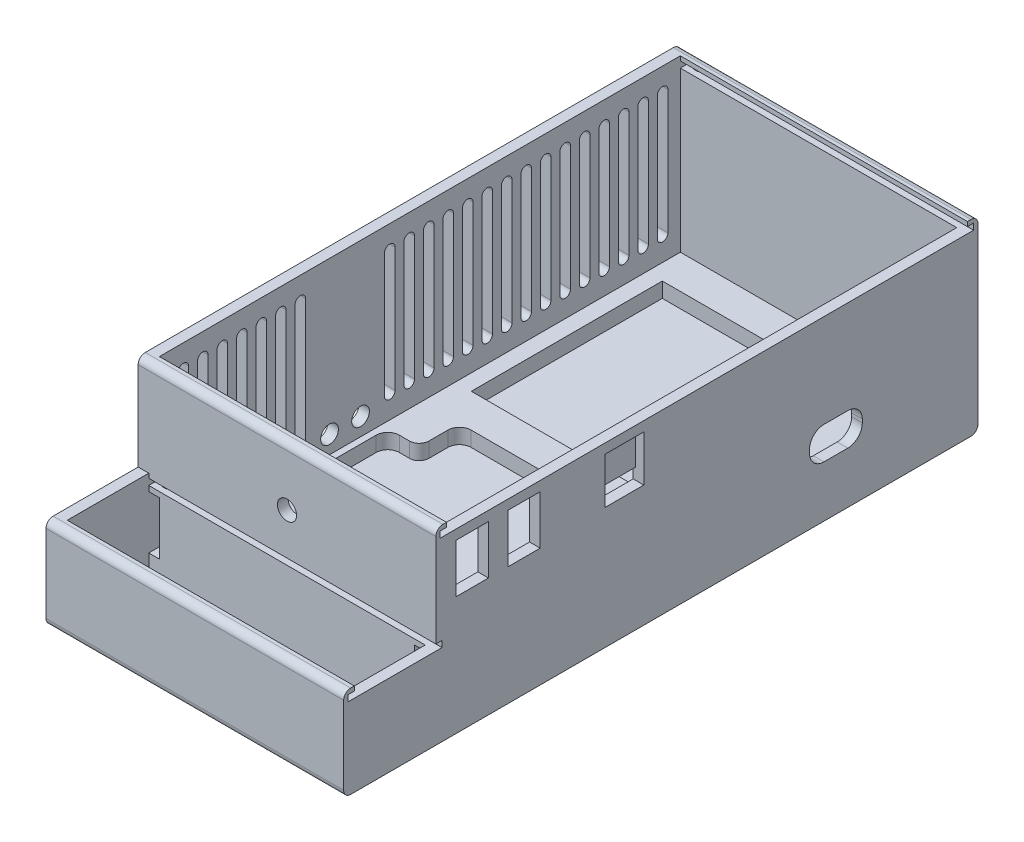
SolidWorks part; units mm, degrees
ref_plane "Front Plane" through (0, 0, 0) normal (0, 0, 1) x (1, 0, 0)
ref_plane "Top Plane" through (0, 0, 0) normal (0, 1, 0) x (1, 0, 0)
ref_plane "Right Plane" through (0, 0, 0) normal (1, 0, 0) x (0, 0, -1)
sketch "Sketch1" plane through (0, 0, 0) normal (0, 1, 0) x (1, 0, 0)
  line L5 (0, 0) -> (100, 0)
  line L6 (0, 0) -> (0, 187)
  line L7 (0, 187) -> (100, 187)
  line L8 (100, 0) -> (100, 187)
  dimension "D1" = 100
  dimension "D2" = 187
extrude "Boss-Extrude1" add sketch "Sketch1" against normal blind 5
sketch "Sketch2" plane through (0, 0, 0) normal (0, 1, 0) x (1, 0, 0)
  line L0 (0, 187) -> (0, 0) construction
  line L1 (11, 11) -> (89, 11)
  line L2 (11, 11) -> (11, 34)
  line L3 (11, 34) -> (89, 34)
  line L4 (89, 11) -> (89, 34)
  line L5 (0, 0) -> (100, 0) construction
  dimension "D1" = 78
  dimension "D2" = 23
  dimension "D3" = 11
  dimension "D4" = 11
extrude "Cut-Extrude1" cut sketch "Sketch2" against normal blind 2.5
sketch "Sketch3" plane through (0, 0, 0) normal (0, 1, 0) x (1, 0, 0)
  line L0 (11, 34) -> (89, 34)
  line L1 (89, 34) -> (89, 11)
  line L2 (89, 11) -> (11, 11)
  line L3 (11, 11) -> (11, 34)
  line L4 (8, 8) -> (8, 37)
  line L5 (8, 37) -> (92, 37)
  line L6 (92, 37) -> (92, 8)
  line L7 (92, 8) -> (8, 8)
  dimension "D1" = 3
extrude "Boss-Extrude2" add sketch "Sketch3" along normal blind 18
sketch "Sketch4" plane through (0, 0, 0) normal (0, 1, 0) x (1, 0, 0)
  line L1 (21.915, 57) -> (31.915, 57) construction
  line L2 (31.915, 47) -> (76.965, 47)
  line L3 (21.915, 107.77) -> (21.915, 102.4)
  line L4 (92, 37) -> (8, 37) construction
  line L5 (24.915, 110.77) -> (76.965, 110.77)
  line L7 (18.915, 99.4) -> (16.035, 99.4)
  line L8 (13.035, 96.4) -> (13.035, 82.01)
  line L9 (86.965, 100.77) -> (86.965, 57)
  line L10 (16.035, 79.01) -> (18.915, 79.01)
  line L11 (13.035, 89.205) -> (0, 89.205) construction
  line L12 (21.915, 76.01) -> (21.915, 57)
  line L14 (86.965, 78.885) -> (100, 78.885) construction
  line L15 (100, 0) -> (100, 187) construction
  line L16 (0, 187) -> (0, 0) construction
  arc A0 (21.915, 57) -> (31.915, 47) centre (31.915, 57) ccw
  arc A6 (24.915, 110.77) -> (21.915, 107.77) centre (24.915, 107.77) ccw
  arc A7 (21.915, 102.4) -> (18.915, 99.4) centre (18.915, 102.4) cw
  arc A8 (16.035, 99.4) -> (13.035, 96.4) centre (16.035, 96.4) ccw
  arc A9 (13.035, 82.01) -> (16.035, 79.01) centre (16.035, 82.01) ccw
  arc A10 (18.915, 79.01) -> (21.915, 76.01) centre (18.915, 76.01) cw
  arc A11 (86.965, 100.77) -> (76.965, 110.77) centre (76.965, 100.77) ccw
  arc A12 (76.965, 47) -> (86.965, 57) centre (76.965, 57) ccw
  point P27 (86.965, 110.77)
  point P29 (86.965, 47)
  dimension "D6" = 62.05
  dimension "D10" = 14.39
  dimension "D1" = 3
  dimension "D2" = 3
  dimension "D8" = 3
  dimension "D9" = 2.88
  dimension "D4" = 10
  dimension "D5" = 10
  dimension "D3" = 10
  dimension "D7" = 10
  dimension "D11" = 5.37
  dimension "D12" = 19.01
  dimension "D13" = 45.05
extrude "Cut-Extrude2" cut sketch "Sketch4" against normal blind 4.25 contours A0 L2 A12 L9 A11 L5 A6 L3 A7 L7 A8 L8 A9 L10 A10 L12
sketch "Sketch7" plane through (0, -2.5, 0) normal (0, 1, 0) x (1, 0, 0)
  line L0 (11, 34) -> (34, 11)
  line L1 (11, 11) -> (89, 11) construction
  line L2 (12, 34) -> (35, 11)
  line L3 (12, 34) -> (13, 34)
  line L5 (11, 11) -> (11.5217, 11)
  line L6 (89, 34) -> (89, 33)
  line L7 (13, 34) -> (36, 11)
  line L8 (14, 34) -> (37, 11)
  line L9 (15, 34) -> (38, 11)
  line L10 (16, 34) -> (39, 11)
  line L11 (17, 34) -> (40, 11)
  line L12 (18, 34) -> (41, 11)
  line L13 (19, 34) -> (42, 11)
  line L14 (20, 34) -> (43, 11)
  line L15 (21, 34) -> (44, 11)
  line L16 (22, 34) -> (45, 11)
  line L17 (23, 34) -> (46, 11)
  line L18 (24, 34) -> (47, 11)
  line L19 (25, 34) -> (48, 11)
  line L20 (26, 34) -> (49, 11)
  line L21 (27, 34) -> (50, 11)
  line L22 (28, 34) -> (51, 11)
  line L23 (29, 34) -> (52, 11)
  line L24 (30, 34) -> (53, 11)
  line L25 (31, 34) -> (54, 11)
  line L26 (32, 34) -> (55, 11)
  line L27 (33, 34) -> (56, 11)
  line L28 (34, 34) -> (57, 11)
  line L29 (35, 34) -> (58, 11)
  line L30 (36, 34) -> (59, 11)
  line L31 (37, 34) -> (60, 11)
  line L32 (38, 34) -> (61, 11)
  line L33 (39, 34) -> (62, 11)
  line L34 (40, 34) -> (63, 11)
  line L35 (41, 34) -> (64, 11)
  line L36 (42, 34) -> (65, 11)
  line L37 (43, 34) -> (66, 11)
  line L38 (44, 34) -> (67, 11)
  line L39 (45, 34) -> (68, 11)
  line L40 (46, 34) -> (69, 11)
  line L41 (47, 34) -> (70, 11)
  line L42 (48, 34) -> (71, 11)
  line L43 (49, 34) -> (72, 11)
  line L44 (50, 34) -> (73, 11)
  line L45 (51, 34) -> (74, 11)
  line L46 (52, 34) -> (75, 11)
  line L47 (53, 34) -> (76, 11)
  line L48 (54, 34) -> (77, 11)
  line L49 (55, 34) -> (78, 11)
  line L50 (56, 34) -> (79, 11)
  line L51 (57, 34) -> (80, 11)
  line L52 (58, 34) -> (81, 11)
  line L53 (59, 34) -> (82, 11)
  line L54 (60, 34) -> (83, 11)
  line L55 (61, 34) -> (84, 11)
  line L56 (62, 34) -> (85, 11)
  line L57 (63, 34) -> (86, 11)
  line L58 (64, 34) -> (87, 11)
  line L59 (65, 34) -> (88, 11)
  line L60 (66, 34) -> (89, 11)
  line L61 (67, 34) -> (89, 12)
  line L62 (68, 34) -> (89, 13)
  line L63 (69, 34) -> (89, 14)
  line L64 (70, 34) -> (89, 15)
  line L65 (71, 34) -> (89, 16)
  line L66 (72, 34) -> (89, 17)
  line L67 (73, 34) -> (89, 18)
  line L68 (74, 34) -> (89, 19)
  line L69 (75, 34) -> (89, 20)
  line L70 (76, 34) -> (89, 21)
  line L71 (77, 34) -> (89, 22)
  line L72 (78, 34) -> (89, 23)
  line L73 (79, 34) -> (89, 24)
  line L74 (80, 34) -> (89, 25)
  line L75 (81, 34) -> (89, 26)
  line L76 (82, 34) -> (89, 27)
  line L77 (83, 34) -> (89, 28)
  line L78 (84, 34) -> (89, 29)
  line L79 (85, 34) -> (89, 30)
  line L80 (86, 34) -> (89, 31)
  line L81 (87, 34) -> (89, 32)
  line L82 (88, 34) -> (89, 33)
  line L83 (11, 32.9783) -> (32.9783, 11)
  line L84 (11, 31.9565) -> (31.9565, 11)
  line L85 (11, 30.9348) -> (30.9348, 11)
  line L86 (11, 29.913) -> (29.913, 11)
  line L87 (11, 28.8913) -> (28.8913, 11)
  line L88 (11, 27.8696) -> (27.8696, 11)
  line L89 (11, 26.8478) -> (26.8478, 11)
  line L90 (11, 25.8261) -> (25.8261, 11)
  line L91 (11, 24.8043) -> (24.8043, 11)
  line L92 (11, 23.7826) -> (23.7826, 11)
  line L93 (11, 22.7609) -> (22.7609, 11)
  line L94 (11, 21.7391) -> (21.7391, 11)
  line L95 (11, 20.7174) -> (20.7174, 11)
  line L96 (11, 19.6956) -> (19.6956, 11)
  line L97 (11, 18.6739) -> (18.6739, 11)
  line L98 (11, 17.6522) -> (17.6522, 11)
  line L99 (11, 16.6304) -> (16.6304, 11)
  line L100 (11, 15.6087) -> (15.6087, 11)
  line L101 (11, 14.5869) -> (14.5869, 11)
  line L102 (11, 13.5652) -> (13.5652, 11)
  line L103 (11, 12.5435) -> (12.5435, 11)
  line L104 (11, 11.5217) -> (11.5217, 11)
  line L105 (12.5435, 11) -> (13.5652, 11)
  line L106 (11, 11.5217) -> (11, 11)
  line L107 (14.5869, 11) -> (15.6087, 11)
  line L108 (11, 13.5652) -> (11, 12.5435)
  line L110 (16.6304, 11) -> (17.6522, 11)
  line L111 (11, 16.6304) -> (11, 17.6522)
  line L112 (11, 18.6739) -> (11, 19.6956)
  line L113 (18.6739, 11) -> (19.6956, 11)
  line L114 (20.7174, 11) -> (21.7391, 11)
  line L115 (11, 20.7174) -> (11, 21.7391)
  line L116 (22.7609, 11) -> (23.7826, 11)
  line L117 (11, 22.7609) -> (11, 23.7826)
  line L118 (11, 24.8043) -> (11, 25.8261)
  line L119 (24.8043, 11) -> (25.8261, 11)
  line L120 (26.8478, 11) -> (27.8696, 11)
  line L121 (11, 26.8478) -> (11, 27.8696)
  line L122 (11, 28.8913) -> (11, 29.913)
  line L123 (11, 30.9348) -> (11, 31.9565)
  line L124 (28.8913, 11) -> (29.913, 11)
  line L125 (30.9348, 11) -> (31.9565, 11)
  line L126 (32.9783, 11) -> (34, 11)
  line L127 (35, 11) -> (36, 11)
  line L128 (11, 32.9783) -> (11, 34)
  line L129 (14, 34) -> (15, 34)
  line L130 (16, 34) -> (17, 34)
  line L131 (37, 11) -> (38, 11)
  line L132 (39, 11) -> (40, 11)
  line L133 (41, 11) -> (42, 11)
  line L134 (43, 11) -> (44, 11)
  line L135 (45, 11) -> (46, 11)
  line L136 (47, 11) -> (48, 11)
  line L137 (49, 11) -> (50, 11)
  line L138 (51, 11) -> (52, 11)
  line L139 (53, 11) -> (54, 11)
  line L140 (55, 11) -> (56, 11)
  line L141 (57, 11) -> (58, 11)
  line L142 (59, 11) -> (60, 11)
  line L143 (61, 11) -> (62, 11)
  line L144 (63, 11) -> (64, 11)
  line L145 (65, 11) -> (66, 11)
  line L146 (18, 34) -> (19, 34)
  line L147 (20, 34) -> (21, 34)
  line L148 (22, 34) -> (23, 34)
  line L149 (24, 34) -> (25, 34)
  line L150 (26, 34) -> (27, 34)
  line L151 (28, 34) -> (29, 34)
  line L152 (30, 34) -> (31, 34)
  line L153 (32, 34) -> (33, 34)
  line L154 (34, 34) -> (35, 34)
  line L155 (36, 34) -> (37, 34)
  line L156 (38, 34) -> (39, 34)
  line L157 (40, 34) -> (41, 34)
  line L158 (42, 34) -> (43, 34)
  line L159 (44, 34) -> (45, 34)
  line L160 (46, 34) -> (47, 34)
  line L161 (67, 11) -> (68, 11)
  line L162 (69, 11) -> (70, 11)
  line L163 (71, 11) -> (72, 11)
  line L164 (73, 11) -> (74, 11)
  line L165 (75, 11) -> (76, 11)
  line L166 (77, 11) -> (78, 11)
  line L167 (79, 11) -> (80, 11)
  line L168 (81, 11) -> (82, 11)
  line L169 (83, 11) -> (84, 11)
  line L170 (85, 11) -> (86, 11)
  line L171 (87, 11) -> (88, 11)
  line L172 (48, 34) -> (49, 34)
  line L173 (50, 34) -> (51, 34)
  line L174 (52, 34) -> (53, 34)
  line L175 (54, 34) -> (55, 34)
  line L176 (56, 34) -> (57, 34)
  line L177 (58, 34) -> (59, 34)
  line L178 (60, 34) -> (61, 34)
  line L179 (62, 34) -> (63, 34)
  line L180 (64, 34) -> (65, 34)
  line L181 (66, 34) -> (67, 34)
  line L182 (68, 34) -> (69, 34)
  line L183 (70, 34) -> (71, 34)
  line L184 (72, 34) -> (73, 34)
  line L185 (74, 34) -> (75, 34)
  line L186 (76, 34) -> (77, 34)
  line L187 (78, 34) -> (79, 34)
  line L188 (80, 34) -> (81, 34)
  line L189 (82, 34) -> (83, 34)
  line L190 (84, 34) -> (85, 34)
  line L191 (86, 34) -> (87, 34)
  line L192 (88, 34) -> (89, 34)
  line L193 (89, 12) -> (89, 11)
  line L194 (89, 14) -> (89, 13)
  line L195 (89, 16) -> (89, 15)
  line L196 (89, 18) -> (89, 17)
  line L197 (89, 20) -> (89, 19)
  line L198 (89, 22) -> (89, 21)
  line L199 (89, 24) -> (89, 23)
  line L200 (89, 26) -> (89, 25)
  line L201 (89, 28) -> (89, 27)
  line L202 (89, 30) -> (89, 29)
  line L203 (89, 32) -> (89, 31)
  line L204 (11, 15.6087) -> (11, 14.5869)
  dimension "D1" = 78
  dimension "D2" = 23
extrude "Cut-Extrude3" cut sketch "Sketch7" against normal blind 0.5
sketch "Sketch8" plane through (0, 0, -37) normal (0, 0, -1) x (-1, 0, 0)
  line L0 (-92, 18) -> (-92, 0) construction
  line L1 (-89, 1.5) -> (-86, 1.5)
  line L2 (-89, 1.5) -> (-89, 16.5)
  line L3 (-89, 16.5) -> (-86, 16.5)
  line L4 (-86, 1.5) -> (-86, 16.5)
  line L5 (-92, 18) -> (-8, 18) construction
  line L6 (-92, 0) -> (-8, 0) construction
  line L7 (-92, 18) -> (-8, 18) construction
  line L8 (-50, 18) -> (-50, 0) construction
  line L9 (-11, 16.5) -> (-14, 16.5)
  line L10 (-14, 1.5) -> (-14, 16.5)
  line L11 (-11, 1.5) -> (-14, 1.5)
  line L12 (-11, 1.5) -> (-11, 16.5)
  dimension "D1" = 3
  dimension "D2" = 1.5
  dimension "D3" = 1.5
  dimension "D4" = 3
extrude "Cut-Extrude4" cut sketch "Sketch8" against normal blind 3
sketch "Sketch9" plane through (8, 0, 0) normal (-1, 0, 0) x (0, 0, 1)
  line L0 (-37, 18) -> (-8, 18)
  line L1 (-8, 18) -> (-8, 21)
  line L2 (-8, 21) -> (-37, 21)
  line L3 (-37, 21) -> (-37, 18)
  dimension "D1" = 3
extrude "Boss-Extrude4" add sketch "Sketch9" against normal blind 3
sketch "Sketch10" plane through (11, 0, 0) normal (1, 0, 0) x (0, 0, -1)
  line L0 (9.25, 18) -> (8, 18)
  line L1 (8, 18) -> (8, 21)
  line L2 (8, 21) -> (11, 21)
  line L3 (8, 21) -> (37, 21) construction
  line L8 (11, 19.75) -> (11, 21)
  line L9 (11, 19.75) -> (9.25, 19.75)
  line L10 (9.25, 19.75) -> (9.25, 18)
  line L12 (8, 18) -> (37, 18) construction
  line L13 (22.5, 21) -> (22.5, 12.8527) construction
  line L22 (35.75, 19.75) -> (35.75, 18)
  line L23 (11, -3) -> (11, 18) construction
  line L24 (34, 19.75) -> (35.75, 19.75)
  line L25 (34, 19.75) -> (34, 21)
  line L26 (37, 21) -> (34, 21)
  line L27 (37, 18) -> (37, 21)
  line L28 (35.75, 18) -> (37, 18)
  dimension "D1" = 1.25
  dimension "D2" = 1.25
extrude "Boss-Extrude5" add sketch "Sketch10" along normal up to surface (81 mm away) up to face at (92, 9, -22.5)
sketch "Sketch12" plane through (0, 0, 0) normal (0, 1, 0) x (1, 0, 0)
  line L0 (0, 0) -> (100, 0)
  line L1 (100, 0) -> (100, 187)
  line L2 (100, 0) -> (100, 187) construction
  line L3 (92, 37) -> (92, 187) construction
  line L4 (100, 187) -> (0, 187) construction
  line L5 (8, 37) -> (8, 187) construction
  line L6 (100, 187) -> (92, 187)
  line L7 (92, 187) -> (92, 8)
  line L8 (92, 8) -> (8, 8)
  line L9 (8, 8) -> (8, 187)
  line L10 (8, 187) -> (0, 187)
  line L11 (0, 187) -> (0, 0)
extrude "Cut-Extrude5" cut sketch "Sketch12" against normal up to surface (5 mm away) up to face at (50, -5, -93.5)
sketch "Sketch13" plane through (0, 0, 0) normal (0, 1, 0) x (1, 0, 0)
  line L0 (8, 37) -> (8, 187)
  line L1 (8, 187) -> (92, 187)
  line L2 (92, 187) -> (92, 37)
  line L5 (11, 40) -> (11, 184)
  line L6 (11, 184) -> (89, 184)
  line L7 (89, 184) -> (89, 40)
  line L8 (11, 40) -> (11, 37)
  line L9 (89, 40) -> (89, 37)
  line L10 (11, 37) -> (8, 37)
  line L11 (89, 40) -> (11, 40) construction
  line L12 (92, 37) -> (8, 37) construction
  line L13 (89, 37) -> (92, 37)
  dimension "D1" = 3
extrude "Boss-Extrude6" add sketch "Sketch13" along normal blind 45
sketch "Sketch14" plane through (0, 0, 0) normal (0, 1, 0) x (1, 0, 0)
  line L11 (84.25, 174.17) -> (15.75, 174.17)
  line L16 (15.75, 120.77) -> (84.25, 120.77)
  line L17 (84.25, 120.77) -> (84.25, 174.17)
  line L20 (24.915, 110.77) -> (76.965, 110.77) construction
  line L22 (15.75, 147.47) -> (11, 147.47) construction
  line L24 (11, 37) -> (11, 184) construction
  line L27 (15.75, 120.77) -> (15.75, 174.17)
  line L28 (84.25, 147.47) -> (89, 147.47) construction
  line L29 (89, 184) -> (89, 37) construction
  dimension "D1" = 68.5
  dimension "D2" = 10
  dimension "D7" = 53.4
extrude "Cut-Extrude6" cut sketch "Sketch14" against normal blind 4.25
sketch "Sketch15" plane through (0, 21, 0) normal (0, 1, 0) x (1, 0, 0)
  line L6 (8, 37) -> (92, 37)
  line L7 (8, 37) -> (8, 34)
  line L8 (8, 34) -> (92, 34)
  line L9 (92, 37) -> (92, 34)
extrude "Boss-Extrude7" add sketch "Sketch15" along normal up to surface (24 mm away) up to face at (50, 45, -111.25)
sketch "Sketch16" plane through (0, 45, 0) normal (0, 1, 0) x (1, 0, 0)
  line L16 (92, 34) -> (8, 34)
  line L17 (8, 34) -> (8, 187)
  line L18 (8, 187) -> (92, 187)
  line L19 (11, 37) -> (92, 37)
  line L20 (92, 34) -> (92, 187) construction
  line L21 (92, 34) -> (92, 37)
  line L22 (11, 37) -> (11, 184)
  line L23 (11, 184) -> (92, 184)
  line L24 (92, 184) -> (92, 187)
extrude "Boss-Extrude8" add sketch "Sketch16" along normal blind 3
sketch "Sketch19" plane through (92, 0, 0) normal (1, 0, 0) x (0, 0, -1)
  line L0 (37, 46.75) -> (35.25, 46.75)
  line L1 (37, 48) -> (37, 45) construction
  line L2 (35.25, 46.75) -> (35.25, 45)
  line L3 (35.25, 45) -> (37, 45)
  line L4 (37, 45) -> (37, 46.75)
  line L5 (110.5, 45) -> (110.5, 48) construction
  line L6 (37, 45) -> (184, 45) construction
  line L7 (184, 45) -> (184, 46.75)
  line L8 (185.75, 45) -> (184, 45)
  line L9 (185.75, 46.75) -> (185.75, 45)
  line L10 (184, 46.75) -> (185.75, 46.75)
  line L11 (34, 48) -> (37, 48) construction
  line L12 (34, 19.75) -> (34, 48) construction
  dimension "D1" = 1.25
  dimension "D2" = 1.25
  dimension "D4" = 3
extrude "Cut-Extrude8" cut sketch "Sketch19" against normal up to surface (81 mm away) up to face at (11, 3.0077, -28.7231)
sketch "Sketch23" plane through (0, 0, -9.25) normal (0, 0, -1) x (-1, 0, 0)
  line L0 (-11, 18.875) -> (-14, 18.875) construction
  line L1 (-11, 18) -> (-11, 19.75) construction
  line L3 (-14.875, 19.5) -> (-13.125, 19.5)
  line L4 (-14.875, 19.5) -> (-14.875, 18.25)
  line L5 (-14.875, 18.25) -> (-13.125, 18.25)
  line L6 (-13.125, 19.5) -> (-13.125, 18.25)
  line L7 (-14.875, 19.5) -> (-13.125, 18.25) construction
  line L8 (-14.875, 18.25) -> (-13.125, 19.5) construction
  dimension "D1" = 3
  dimension "D2" = 1.75
  dimension "D3" = 1.25
extrude "Boss-Extrude9" add sketch "Sketch23" along normal blind 0.4
fillet "Fillet2" radius 0.4 2 edges at (13.125, 18.875, -9.65) (14.875, 18.875, -9.65)
sketch "Sketch40" plane through (0, 0, -35.75) normal (0, 0, 1) x (1, 0, 0)
  line L0 (11, 18.875) -> (14, 18.875) construction
  line L1 (11, 19.75) -> (11, 18) construction
  line L3 (13.125, 19.5) -> (14.875, 19.5)
  line L4 (13.125, 19.5) -> (13.125, 18.25)
  line L5 (13.125, 18.25) -> (14.875, 18.25)
  line L6 (14.875, 19.5) -> (14.875, 18.25)
  line L7 (13.125, 19.5) -> (14.875, 18.25) construction
  line L8 (13.125, 18.25) -> (14.875, 19.5) construction
  dimension "D1" = 3
  dimension "D2" = 1.25
  dimension "D3" = 1.75
extrude "Boss-Extrude14" add sketch "Sketch40" along normal blind 0.4
fillet "Fillet6" radius 0.4 2 edges at (14.875, 18.875, -35.35) (13.125, 18.875, -35.35)
sketch "Sketch25" plane through (0, 0, -35.25) normal (0, 0, -1) x (-1, 0, 0)
  line L0 (-11, 45.875) -> (-14, 45.875) construction
  line L1 (-11, 46.75) -> (-11, 45) construction
  line L3 (-13.125, 46.5) -> (-14.875, 46.5)
  line L4 (-13.125, 46.5) -> (-13.125, 45.25)
  line L5 (-13.125, 45.25) -> (-14.875, 45.25)
  line L6 (-14.875, 46.5) -> (-14.875, 45.25)
  line L7 (-13.125, 46.5) -> (-14.875, 45.25) construction
  line L8 (-13.125, 45.25) -> (-14.875, 46.5) construction
  dimension "D1" = 3
  dimension "D2" = 1.75
  dimension "D3" = 1.25
extrude "Boss-Extrude11" add sketch "Sketch25" along normal blind 0.4
fillet "Fillet4" radius 0.4 2 edges at (13.125, 45.875, -35.65) (14.875, 45.875, -35.65)
sketch "Sketch26" plane through (0, 0, -185.75) normal (0, 0, 1) x (1, 0, 0)
  line L0 (11, 45.875) -> (14, 45.875) construction
  line L1 (11, 45) -> (11, 46.75) construction
  line L3 (13.125, 46.5) -> (14.875, 46.5)
  line L4 (13.125, 46.5) -> (13.125, 45.25)
  line L5 (13.125, 45.25) -> (14.875, 45.25)
  line L6 (14.875, 46.5) -> (14.875, 45.25)
  line L7 (13.125, 46.5) -> (14.875, 45.25) construction
  line L8 (13.125, 45.25) -> (14.875, 46.5) construction
  dimension "D1" = 3
  dimension "D2" = 1.75
  dimension "D3" = 1.25
extrude "Boss-Extrude12" add sketch "Sketch26" along normal blind 0.4
fillet "Fillet5" radius 0.4 2 edges at (13.125, 45.875, -185.35) (14.875, 45.875, -185.35)
sketch "Sketch27" plane through (92, 0, 0) normal (1, 0, 0) x (0, 0, -1)
  line L0 (34, 19.75) -> (34, 48) construction
  line L1 (82, 42) -> (92.45, 42)
  line L2 (82, 42) -> (82, 29.5)
  line L3 (82, 29.5) -> (92.45, 29.5)
  line L4 (92.45, 42) -> (92.45, 29.5)
  line L7 (35.25, 45) -> (185.75, 45) construction
  dimension "D1" = 12.5
  dimension "D2" = 10.45
  dimension "D3" = 48
  dimension "D4" = 3
extrude "Cut-Extrude10" cut sketch "Sketch27" against normal up to surface (3 mm away) up to face at (89, 0.5702, -29.386)
sketch "Sketch29" plane through (92, 0, 0) normal (1, 0, 0) x (0, 0, -1)
  line L0 (34, 19.75) -> (34, 48) construction
  line L1 (40, 42) -> (48.6, 42)
  line L2 (40, 42) -> (40, 28.7)
  line L3 (40, 28.7) -> (48.6, 28.7)
  line L4 (48.6, 42) -> (48.6, 28.7)
  line L5 (54.6, 42) -> (63.2, 42)
  line L6 (54.6, 42) -> (54.6, 28.7)
  line L7 (54.6, 28.7) -> (63.2, 28.7)
  line L8 (63.2, 42) -> (63.2, 28.7)
  line L10 (35.25, 45) -> (185.75, 45) construction
  dimension "D1" = 8.6
  dimension "D2" = 8.6
  dimension "D3" = 13.3
  dimension "D4" = 13.3
  dimension "D5" = 6
  dimension "D6" = 6
  dimension "D7" = 3
extrude "Cut-Extrude11" cut sketch "Sketch29" against normal up to surface (3 mm away) up to face at (89, 35.75, -87.225)
sketch "Sketch30" plane through (0, 0, -34) normal (0, 0, 1) x (1, 0, 0)
  line L0 (92, 18) -> (8, 48) construction
  line L1 (92, 19.75) -> (92, 48) construction
  line L2 (50, 33) -> (50, 31.5) construction
  circle A2 centre (50, 31.5) radius 2.5
  dimension "D1" = 1.5
  dimension "D2" = 5
extrude "Cut-Extrude12" cut sketch "Sketch30" against normal up to surface (3 mm away) up to face at (51.5, 47.375, -37)
sketch "Sketch31" plane through (92, 0, 0) normal (1, 0, 0) x (0, 0, -1)
  line L0 (187, -5) -> (8, -5) construction
  line L1 (143.55, 12.5) -> (150.25, 12.5)
  line L2 (142.45, 13.6) -> (142.45, 14.55)
  line L3 (143.55, 15.65) -> (150.25, 15.65)
  line L4 (151.35, 13.6) -> (151.35, 14.55)
  line L5 (187, -5) -> (187, 48) construction
  arc A0 (150.25, 15.65) -> (151.35, 14.55) centre (150.25, 14.55) cw
  arc A1 (150.25, 12.5) -> (151.35, 13.6) centre (150.25, 13.6) ccw
  arc A2 (143.55, 12.5) -> (142.45, 13.6) centre (143.55, 13.6) cw
  arc A3 (142.45, 14.55) -> (143.55, 15.65) centre (143.55, 14.55) cw
  point P14 (151.35, 12.5)
  point P17 (142.45, 12.5)
  dimension "D5" = 1.1
  dimension "D1" = 0.95
  dimension "D2" = 35.65
  dimension "D3" = 17.5
  dimension "D4" = 6.7
extrude "Cut-Extrude13" cut sketch "Sketch31" against normal up to surface (3 mm away) up to face at (89, 35.35, -44.3)
sketch "Sketch33" plane through (11, 0, 0) normal (1, 0, 0) x (0, 0, -1)
  line L0 (179, 6.5) -> (179, 41.5) construction
  line L1 (177.5, 6.5) -> (177.5, 41.5)
  line L2 (180.5, 6.5) -> (180.5, 41.5)
  line L3 (184, 45) -> (184, 0) construction
  line L4 (37, 1.5) -> (78.76, 1.5) construction
  line L5 (179, 5) -> (179, 0) construction
  line L6 (37, 0) -> (184, 0) construction
  line L7 (179, 43) -> (179, 48) construction
  line L8 (173.5, 6.5) -> (173.5, 41.5) construction
  line L9 (172, 6.5) -> (172, 41.5)
  line L10 (175, 6.5) -> (175, 41.5)
  line L11 (168, 6.5) -> (168, 41.5) construction
  line L12 (166.5, 6.5) -> (166.5, 41.5)
  line L13 (169.5, 6.5) -> (169.5, 41.5)
  line L14 (162.5, 6.5) -> (162.5, 41.5) construction
  line L15 (161, 6.5) -> (161, 41.5)
  line L16 (164, 6.5) -> (164, 41.5)
  line L17 (157, 6.5) -> (157, 41.5) construction
  line L18 (155.5, 6.5) -> (155.5, 41.5)
  line L19 (158.5, 6.5) -> (158.5, 41.5)
  line L20 (151.5, 6.5) -> (151.5, 41.5) construction
  line L21 (150, 6.5) -> (150, 41.5)
  line L22 (153, 6.5) -> (153, 41.5)
  line L23 (146, 6.5) -> (146, 41.5) construction
  line L24 (144.5, 6.5) -> (144.5, 41.5)
  line L25 (147.5, 6.5) -> (147.5, 41.5)
  line L26 (140.5, 6.5) -> (140.5, 41.5) construction
  line L27 (139, 6.5) -> (139, 41.5)
  line L28 (142, 6.5) -> (142, 41.5)
  line L29 (135, 6.5) -> (135, 41.5) construction
  line L30 (133.5, 6.5) -> (133.5, 41.5)
  line L31 (136.5, 6.5) -> (136.5, 41.5)
  line L32 (129.5, 6.5) -> (129.5, 41.5) construction
  line L33 (128, 6.5) -> (128, 41.5)
  line L34 (131, 6.5) -> (131, 41.5)
  line L35 (124, 6.5) -> (124, 41.5) construction
  line L36 (122.5, 6.5) -> (122.5, 41.5)
  line L37 (125.5, 6.5) -> (125.5, 41.5)
  line L38 (118.5, 6.5) -> (118.5, 41.5) construction
  line L39 (117, 6.5) -> (117, 41.5)
  line L40 (120, 6.5) -> (120, 41.5)
  line L41 (113, 6.5) -> (113, 41.5) construction
  line L42 (111.5, 6.5) -> (111.5, 41.5)
  line L43 (114.5, 6.5) -> (114.5, 41.5)
  line L44 (107.5, 6.5) -> (107.5, 41.5) construction
  line L45 (106, 6.5) -> (106, 41.5)
  line L46 (109, 6.5) -> (109, 41.5)
  line L47 (102, 6.5) -> (102, 41.5) construction
  line L48 (100.5, 6.5) -> (100.5, 41.5)
  line L49 (103.5, 6.5) -> (103.5, 41.5)
  line L50 (78.76, 1.5) -> (85.01, 1.5) construction
  line L53 (85.01, 1.5) -> (93.76, 1.5) construction
  line L56 (85.01, 5) -> (85.01, 1.5) construction
  line L59 (93.76, 1.5) -> (93.76, 5) construction
  line L62 (37, 48) -> (184, 48) construction
  line L64 (102, 5) -> (93.76, 5) construction
  line L65 (93.76, 5) -> (85.01, 5) construction
  line L67 (93.76, 5) -> (85.01, 5) construction
  line L68 (89.385, 5) -> (89.385, 41.5) construction
  line L69 (76.77, 6.5) -> (76.77, 41.5) construction
  line L70 (78.27, 6.5) -> (78.27, 41.5)
  line L71 (75.27, 6.5) -> (75.27, 41.5)
  line L72 (71.27, 6.5) -> (71.27, 41.5) construction
  line L73 (72.77, 6.5) -> (72.77, 41.5)
  line L74 (69.77, 6.5) -> (69.77, 41.5)
  line L75 (65.77, 6.5) -> (65.77, 41.5) construction
  line L76 (67.27, 6.5) -> (67.27, 41.5)
  line L77 (64.27, 6.5) -> (64.27, 41.5)
  line L78 (60.27, 6.5) -> (60.27, 41.5) construction
  line L79 (61.77, 6.5) -> (61.77, 41.5)
  line L80 (58.77, 6.5) -> (58.77, 41.5)
  line L81 (54.77, 6.5) -> (54.77, 41.5) construction
  line L82 (56.27, 6.5) -> (56.27, 41.5)
  line L83 (53.27, 6.5) -> (53.27, 41.5)
  line L84 (49.27, 6.5) -> (49.27, 41.5) construction
  line L85 (50.77, 6.5) -> (50.77, 41.5)
  line L86 (47.77, 6.5) -> (47.77, 41.5)
  line L87 (43.77, 6.5) -> (43.77, 41.5) construction
  line L88 (45.27, 6.5) -> (45.27, 41.5)
  line L89 (42.27, 6.5) -> (42.27, 41.5)
  arc A0 (177.5, 6.5) -> (180.5, 6.5) centre (179, 6.5) ccw
  arc A1 (180.5, 41.5) -> (177.5, 41.5) centre (179, 41.5) ccw
  arc A2 (172, 6.5) -> (175, 6.5) centre (173.5, 6.5) ccw
  arc A3 (175, 41.5) -> (172, 41.5) centre (173.5, 41.5) ccw
  arc A4 (166.5, 6.5) -> (169.5, 6.5) centre (168, 6.5) ccw
  arc A5 (169.5, 41.5) -> (166.5, 41.5) centre (168, 41.5) ccw
  arc A6 (161, 6.5) -> (164, 6.5) centre (162.5, 6.5) ccw
  arc A7 (164, 41.5) -> (161, 41.5) centre (162.5, 41.5) ccw
  arc A8 (155.5, 6.5) -> (158.5, 6.5) centre (157, 6.5) ccw
  arc A9 (158.5, 41.5) -> (155.5, 41.5) centre (157, 41.5) ccw
  arc A10 (150, 6.5) -> (153, 6.5) centre (151.5, 6.5) ccw
  arc A11 (153, 41.5) -> (150, 41.5) centre (151.5, 41.5) ccw
  arc A12 (144.5, 6.5) -> (147.5, 6.5) centre (146, 6.5) ccw
  arc A13 (147.5, 41.5) -> (144.5, 41.5) centre (146, 41.5) ccw
  arc A14 (139, 6.5) -> (142, 6.5) centre (140.5, 6.5) ccw
  arc A15 (142, 41.5) -> (139, 41.5) centre (140.5, 41.5) ccw
  arc A16 (133.5, 6.5) -> (136.5, 6.5) centre (135, 6.5) ccw
  arc A17 (136.5, 41.5) -> (133.5, 41.5) centre (135, 41.5) ccw
  arc A18 (128, 6.5) -> (131, 6.5) centre (129.5, 6.5) ccw
  arc A19 (131, 41.5) -> (128, 41.5) centre (129.5, 41.5) ccw
  arc A20 (122.5, 6.5) -> (125.5, 6.5) centre (124, 6.5) ccw
  arc A21 (125.5, 41.5) -> (122.5, 41.5) centre (124, 41.5) ccw
  arc A22 (117, 6.5) -> (120, 6.5) centre (118.5, 6.5) ccw
  arc A23 (120, 41.5) -> (117, 41.5) centre (118.5, 41.5) ccw
  arc A24 (111.5, 6.5) -> (114.5, 6.5) centre (113, 6.5) ccw
  arc A25 (114.5, 41.5) -> (111.5, 41.5) centre (113, 41.5) ccw
  arc A26 (106, 6.5) -> (109, 6.5) centre (107.5, 6.5) ccw
  arc A27 (109, 41.5) -> (106, 41.5) centre (107.5, 41.5) ccw
  arc A28 (100.5, 6.5) -> (103.5, 6.5) centre (102, 6.5) ccw
  arc A29 (103.5, 41.5) -> (100.5, 41.5) centre (102, 41.5) ccw
  circle A38 centre (85.01, 5) radius 2.5
  circle A39 centre (93.76, 5) radius 2.5
  arc A40 (78.27, 6.5) -> (75.27, 6.5) centre (76.77, 6.5) cw
  arc A41 (75.27, 41.5) -> (78.27, 41.5) centre (76.77, 41.5) cw
  arc A42 (72.77, 6.5) -> (69.77, 6.5) centre (71.27, 6.5) cw
  arc A43 (69.77, 41.5) -> (72.77, 41.5) centre (71.27, 41.5) cw
  arc A44 (67.27, 6.5) -> (64.27, 6.5) centre (65.77, 6.5) cw
  arc A45 (64.27, 41.5) -> (67.27, 41.5) centre (65.77, 41.5) cw
  arc A46 (61.77, 6.5) -> (58.77, 6.5) centre (60.27, 6.5) cw
  arc A47 (58.77, 41.5) -> (61.77, 41.5) centre (60.27, 41.5) cw
  arc A48 (56.27, 6.5) -> (53.27, 6.5) centre (54.77, 6.5) cw
  arc A49 (53.27, 41.5) -> (56.27, 41.5) centre (54.77, 41.5) cw
  arc A50 (50.77, 6.5) -> (47.77, 6.5) centre (49.27, 6.5) cw
  arc A51 (47.77, 41.5) -> (50.77, 41.5) centre (49.27, 41.5) cw
  arc A52 (45.27, 6.5) -> (42.27, 6.5) centre (43.77, 6.5) cw
  arc A53 (42.27, 41.5) -> (45.27, 41.5) centre (43.77, 41.5) cw
  point P2 (179, 24)
  point P21 (173.5, 24)
  point P28 (168, 24)
  point P35 (162.5, 24)
  point P42 (157, 24)
  point P49 (151.5, 24)
  point P56 (146, 24)
  point P63 (140.5, 24)
  point P70 (135, 24)
  point P77 (129.5, 24)
  point P84 (124, 24)
  point P91 (118.5, 24)
  point P98 (113, 24)
  point P105 (107.5, 24)
  point P112 (102, 24)
  point P130 (76.77, 24)
  point P137 (71.27, 24)
  point P145 (65.77, 24)
  point P152 (60.27, 24)
  point P159 (54.77, 24)
  point P166 (49.27, 24)
  point P173 (43.77, 24)
  dimension "D2" = 1.5
  dimension "D5" = 5.5
  dimension "D6" = 5
  dimension "D7" = 5
  dimension "D1" = 35
  dimension "D3" = 5
  dimension "D8" = 41.76
  dimension "D9" = 6.25
  dimension "D10" = 8.75
  dimension "D12" = 5.5
  dimension "D4" = 15
  dimension "D11" = 7
extrude "Cut-Extrude15" cut sketch "Sketch33" against normal up to surface (3 mm away) up to face at (8, 21.3333, -76.3333)
sketch "Sketch34" plane through (0, 0, 0) normal (0, 1, 0) x (1, 0, 0)
  line L165 (87.215, 57) -> (87.215, 100.77)
  line L166 (31.915, 46.75) -> (76.965, 46.75)
  line L167 (21.665, 76.01) -> (21.665, 57)
  line L168 (16.035, 78.76) -> (18.915, 78.76)
  line L169 (12.785, 96.4) -> (12.785, 82.01)
  line L170 (18.915, 99.65) -> (16.035, 99.65)
  line L171 (21.665, 107.77) -> (21.665, 102.4)
  line L172 (76.965, 111.02) -> (24.915, 111.02)
  line L173 (87.215, 57) -> (87.215, 100.77)
  line L174 (31.915, 46.75) -> (76.965, 46.75)
  line L175 (21.665, 76.01) -> (21.665, 57)
  line L176 (16.035, 78.76) -> (18.915, 78.76)
  line L177 (12.785, 96.4) -> (12.785, 82.01)
  line L178 (18.915, 99.65) -> (16.035, 99.65)
  line L179 (21.665, 107.77) -> (21.665, 102.4)
  line L180 (76.965, 111.02) -> (24.915, 111.02)
  line L187 (15.5, 174.42) -> (15.5, 120.52)
  line L188 (15.5, 120.52) -> (84.5, 120.52)
  line L189 (84.5, 120.52) -> (84.5, 174.42)
  line L190 (84.5, 174.42) -> (15.5, 174.42)
  line L191 (15.5, 174.42) -> (15.5, 120.52)
  line L192 (15.5, 120.52) -> (84.5, 120.52)
  line L193 (84.5, 120.52) -> (84.5, 174.42)
  line L194 (84.5, 174.42) -> (15.5, 174.42)
  arc A168 (87.215, 100.77) -> (76.965, 111.02) centre (76.965, 100.77) ccw
  arc A169 (76.965, 46.75) -> (87.215, 57) centre (76.965, 57) ccw
  arc A170 (21.665, 57) -> (31.915, 46.75) centre (31.915, 57) ccw
  arc A171 (21.665, 76.01) -> (18.915, 78.76) centre (18.915, 76.01) ccw
  arc A172 (12.785, 82.01) -> (16.035, 78.76) centre (16.035, 82.01) ccw
  arc A173 (16.035, 99.65) -> (12.785, 96.4) centre (16.035, 96.4) ccw
  arc A174 (18.915, 99.65) -> (21.665, 102.4) centre (18.915, 102.4) ccw
  arc A175 (24.915, 111.02) -> (21.665, 107.77) centre (24.915, 107.77) ccw
  arc A176 (87.215, 100.77) -> (76.965, 111.02) centre (76.965, 100.77) ccw
  arc A177 (76.965, 46.75) -> (87.215, 57) centre (76.965, 57) ccw
  arc A178 (21.665, 57) -> (31.915, 46.75) centre (31.915, 57) ccw
  arc A179 (21.665, 76.01) -> (18.915, 78.76) centre (18.915, 76.01) ccw
  arc A180 (12.785, 82.01) -> (16.035, 78.76) centre (16.035, 82.01) ccw
  arc A181 (16.035, 99.65) -> (12.785, 96.4) centre (16.035, 96.4) ccw
  arc A182 (18.915, 99.65) -> (21.665, 102.4) centre (18.915, 102.4) ccw
  arc A183 (24.915, 111.02) -> (21.665, 107.77) centre (24.915, 107.77) ccw
  dimension "D1" = 0.25
  dimension "D2" = 0.25
extrude "Cut-Extrude16" cut sketch "Sketch34" against normal up to surface (4.25 mm away) up to face at (35.6106, -4.25, -84.3919)
sketch "Sketch36" plane through (92, 0, 0) normal (1, 0, 0) x (0, 0, -1)
  line L14 (81.75, 29.25) -> (92.7, 29.25)
  line L15 (81.75, 42.25) -> (81.75, 29.25)
  line L16 (92.7, 29.25) -> (92.7, 42.25)
  line L17 (92.7, 42.25) -> (81.75, 42.25)
  line L18 (81.75, 29.25) -> (92.7, 29.25)
  line L19 (81.75, 42.25) -> (81.75, 29.25)
  line L20 (39.75, 42.25) -> (39.75, 28.45)
  line L21 (39.75, 28.45) -> (48.85, 28.45)
  line L22 (48.85, 28.45) -> (48.85, 42.25)
  line L23 (48.85, 42.25) -> (39.75, 42.25)
  line L24 (39.75, 42.25) -> (39.75, 28.45)
  line L25 (39.75, 28.45) -> (48.85, 28.45)
  line L26 (48.85, 28.45) -> (48.85, 42.25)
  line L27 (48.85, 42.25) -> (39.75, 42.25)
  line L28 (92.7, 29.25) -> (92.7, 42.25)
  line L29 (92.7, 42.25) -> (81.75, 42.25)
  line L38 (54.35, 28.45) -> (63.45, 28.45)
  line L39 (54.35, 42.25) -> (54.35, 28.45)
  line L40 (63.45, 28.45) -> (63.45, 42.25)
  line L41 (63.45, 42.25) -> (54.35, 42.25)
  line L42 (54.35, 28.45) -> (63.45, 28.45)
  line L43 (54.35, 42.25) -> (54.35, 28.45)
  line L44 (63.45, 28.45) -> (63.45, 42.25)
  line L45 (63.45, 42.25) -> (54.35, 42.25)
  dimension "D1" = 0.25
  dimension "D2" = 0.25
  dimension "D3" = 0.25
extrude "Cut-Extrude18" cut sketch "Sketch36" against normal up to surface (3 mm away) up to face at (89, 14.075, -146.9)
sketch "Sketch37" plane through (0, 0, -34) normal (0, 0, 1) x (1, 0, 0)
  circle A2 centre (50, 31.5) radius 2.7
  circle A4 centre (50, 31.5) radius 2.7
  dimension "D1" = 0.2
extrude "Cut-Extrude19" cut sketch "Sketch37" against normal up to surface (3 mm away) up to face at (51.5, 47.375, -37)
sketch "Sketch38" plane through (89, 0, 0) normal (-1, 0, 0) x (0, 0, 1)
  line L5 (-81.75, 29.25) -> (-81.75, 42.25) construction
  line L6 (-92.7, 42.25) -> (-81.75, 42.25)
  line L7 (-92.7, 42.25) -> (-92.7, 32.39)
  line L8 (-92.7, 32.39) -> (-81.75, 32.39)
  line L9 (-81.75, 42.25) -> (-81.75, 32.39)
  line L10 (-92.7, 29.25) -> (-81.75, 29.25) construction
  dimension "D1" = 3.14
extrude "Boss-Extrude13" add sketch "Sketch38" against normal blind 0.6
sketch "Sketch39" plane through (92, 0, 0) normal (1, 0, 0) x (0, 0, -1)
  line L27 (154.35, 13.6) -> (154.35, 14.55)
  line L28 (143.55, 9.5) -> (150.25, 9.5)
  line L29 (139.45, 14.55) -> (139.45, 13.6)
  line L30 (150.25, 18.65) -> (143.55, 18.65)
  line L31 (154.35, 13.6) -> (154.35, 14.55)
  line L32 (143.55, 9.5) -> (150.25, 9.5)
  line L33 (139.45, 14.55) -> (139.45, 13.6)
  line L34 (150.25, 18.65) -> (143.55, 18.65)
  arc A20 (154.35, 14.55) -> (150.25, 18.65) centre (150.25, 14.55) ccw
  arc A21 (150.25, 9.5) -> (154.35, 13.6) centre (150.25, 13.6) ccw
  arc A22 (139.45, 13.6) -> (143.55, 9.5) centre (143.55, 13.6) ccw
  arc A23 (143.55, 18.65) -> (139.45, 14.55) centre (143.55, 14.55) ccw
  arc A24 (154.35, 14.55) -> (150.25, 18.65) centre (150.25, 14.55) ccw
  arc A25 (150.25, 9.5) -> (154.35, 13.6) centre (150.25, 13.6) ccw
  arc A26 (139.45, 13.6) -> (143.55, 9.5) centre (143.55, 13.6) ccw
  arc A27 (143.55, 18.65) -> (139.45, 14.55) centre (143.55, 14.55) ccw
  dimension "D1" = 3
extrude "Cut-Extrude20" cut sketch "Sketch39" against normal up to surface (3 mm away) up to face at (89, 35.35, -44.3)
fillet "Fillet18" radius 2 5 edges at (50, -5, -187) (50, 48, -187) (50, 48, -34) (50, -5, -8) (50, 21, -8)
